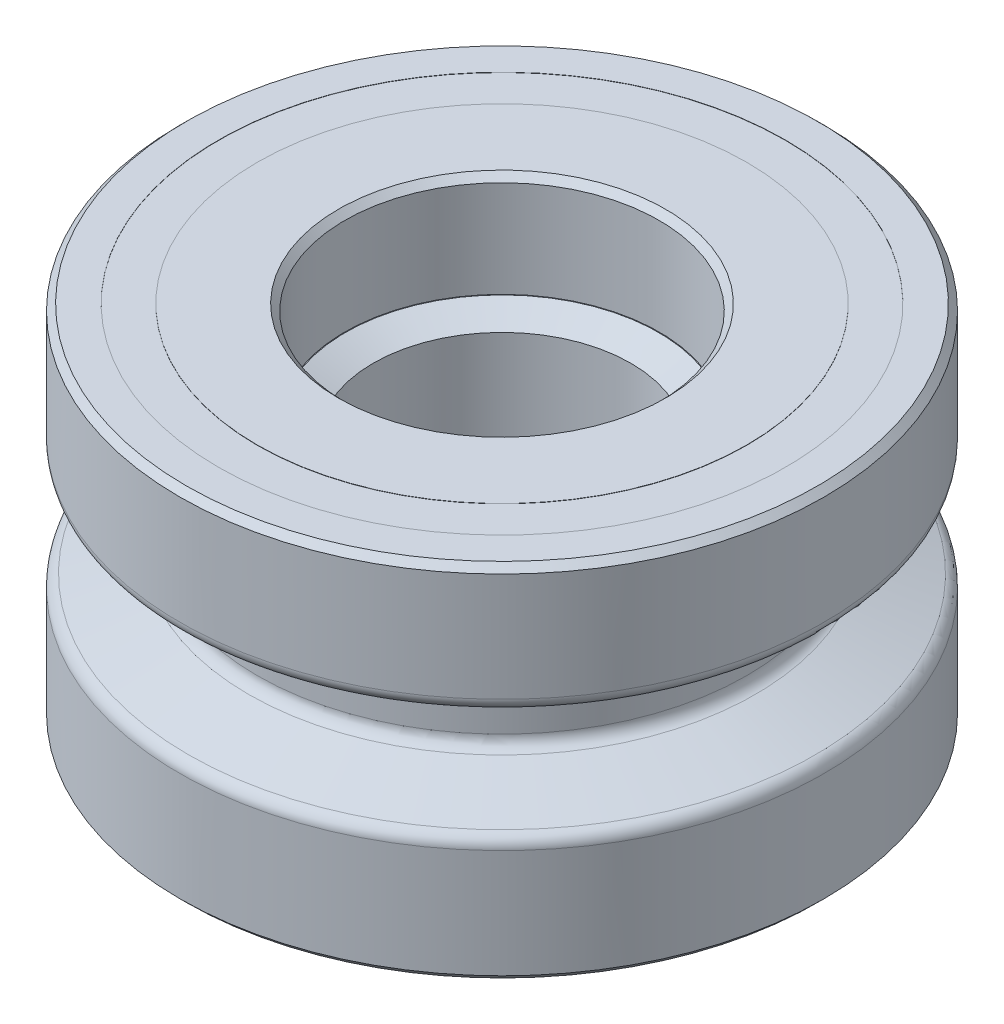
SolidWorks part; units mm, degrees
ref_plane "Front Plane" through (0, 0, 0) normal (0, 0, 1) x (1, 0, 0)
ref_plane "Top Plane" through (0, 0, 0) normal (0, 1, 0) x (1, 0, 0)
ref_plane "Right Plane" through (0, 0, 0) normal (1, 0, 0) x (0, 0, -1)
sketch "Sketch1" plane through (0, 0, 0) normal (0, 1, 0) x (1, 0, 0)
  circle A0 centre (0, 0) radius 12.5
  dimension "D1" = 25
extrude "Boss-Extrude1" add sketch "Sketch1" along normal mid plane 14
sketch "Sketch2" plane through (0, -7, 0) normal (0, -1, 0) x (1, 0, 0)
  circle A1 centre (0, 0) radius 5
  dimension "D1" = 10
extrude "Cut-Extrude1" cut sketch "Sketch2" against normal up to next
sketch "Sketch11" plane through (0, -7, 0) normal (0, -1, 0) x (1, 0, 0)
  circle A0 centre (0, 0) radius 6.1
  dimension "D1" = 12.2
extrude "Cut-Extrude5" cut sketch "Sketch11" against normal blind 4
sketch "Sketch12" plane through (0, 7, 0) normal (0, 1, 0) x (1, 0, 0)
  circle A0 centre (0, 0) radius 6.1 construction
  circle A1 centre (0, 0) radius 6.1
extrude "Cut-Extrude6" cut sketch "Sketch12" against normal blind 4
sketch "Sketch7" plane through (0, 7, 0) normal (0, 1, 0) x (1, 0, 0)
  circle A1 centre (0, 0) radius 9.5
  circle A2 centre (0, 0) radius 11
  circle A3 centre (0, 0) radius 11
  dimension "D1" = 1.5
  dimension "D2" = 1.5
extrude "Cut-Extrude4" cut sketch "Sketch7" against normal blind 0.01 contours A3 A1 region at (-10.6889, 7, 0)
ref_axis "Axis1" through (0, 7, 0) along (0, -1, 0)
sketch "Sketch10" plane through (0, 0, 0) normal (0, 0, 1) x (1, 0, 0)
  line L0 (-4.2808, 0) -> (5.2603, 0) construction
  line L1 (12.5, 2.1919) -> (9.5, 1.1)
  line L2 (12.5, -7) -> (12.5, 7) construction
  line L4 (12.5, -2.1919) -> (9.5, -1.1)
  line L5 (12.5, 2.1919) -> (12.5, -2.1919)
  line L6 (9.5, 1.1) -> (9.5, -1.1)
  line L7 (9.5, 1.1) -> (12.5, 1.1) construction
  dimension "D1" = 3
  dimension "D2" = 2.2
  dimension "D3" = 20
revolve "Cut-Revolve1" cut sketch "Sketch10" angle 360 about axis through (0, 7, 0) along (0, -1, 0)
chamfer "Chamfer2" distance 0.5 angle 65 1 edges at (0, 3, 5) first distance on face at (0, -3, -5)
fillet "Fillet4" radius 0.5 4 edges at (0, -1.1, 9.5) (0, 1.1, 9.5) (0, 2.1919, 12.5) (0, -2.1919, 12.5)
chamfer "Chamfer1" distance 0.25 angle 45 5 edges at (0, -7, 12.5) (0, 7, 12.5) (0, -7, -6.1) (0, 7, 6.1) (0, -3, -5)
